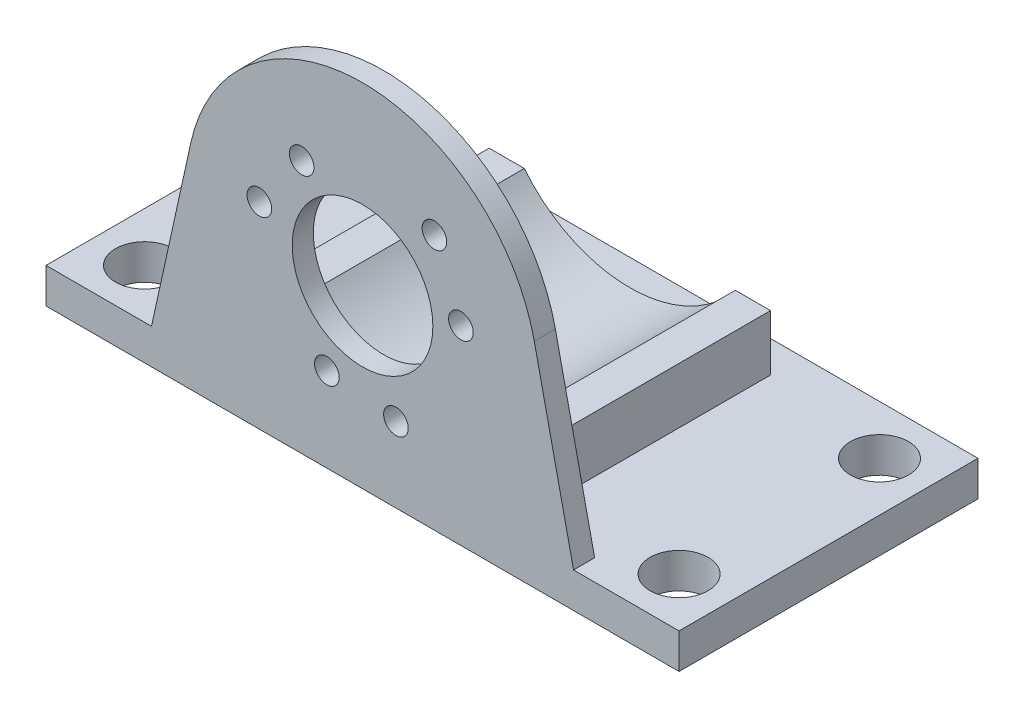
SolidWorks part; units mm, degrees
material "Plain Carbon Steel"
ref_plane "Front Plane" through (0, 0, 0) normal (0, 0, 1) x (1, 0, 0)
ref_plane "Top Plane" through (0, 0, 0) normal (0, 1, 0) x (1, 0, 0)
ref_plane "Right Plane" through (0, 0, 0) normal (1, 0, 0) x (0, 0, -1)
sketch "Sketch3" plane through (0, 0, 0) normal (0, 1, 0) x (1, 0, 0)
  line L0 (-40.6832, 0) -> (52.6999, 0) construction
  line L1 (-45, 21.25) -> (45, 21.25)
  line L2 (-45, 21.25) -> (-45, -21.25)
  line L3 (-45, -21.25) -> (45, -21.25)
  line L4 (45, 21.25) -> (45, -21.25)
  line L5 (0, 26.2262) -> (0, -26.6116) construction
  circle A0 centre (-38, 14.25) radius 4.125
  circle A4 centre (38, 14.25) radius 4.125
  circle A5 centre (38, -14.25) radius 4.125
  circle A6 centre (-38, -14.25) radius 4.125
  point P0 (0, -21.25)
  point P5 (45, 0)
  dimension "D5" = 8.25
  dimension "D1" = 42.5
  dimension "D2" = 90
  dimension "D3" = 7
  dimension "D4" = 7
extrude "Boss-Extrude1" add sketch "Sketch3" along normal blind 5
sketch "Sketch4" plane through (0, 0, 21.25) normal (0, 0, 1) x (1, 0, 0)
  line L2 (30, 5) -> (24.4157, 30.3735)
  line L3 (-30, 5) -> (-24.4157, 30.3735)
  line L4 (-45, 5) -> (45, 5) construction
  line L6 (-30, 5) -> (30, 5)
  circle A1 centre (0, 25) radius 19
  circle A2 centre (0, 25) radius 3
  circle A3 centre (13.9904, 27.0801) radius 1.75
  circle A4 centre (10.2192, 36.3473) radius 1.75
  circle A5 centre (-8.6549, 36.0875) radius 1.75
  circle A6 centre (-14.6673, 27.9923) radius 1.75
  circle A7 centre (-5.0673, 12.0109) radius 1.75
  circle A8 centre (4.7494, 10.6747) radius 1.75
  circle A9 centre (0, 25) radius 10
  arc A10 (24.4157, 30.3735) -> (-24.4157, 30.3735) centre (0, 25) ccw
  point P8 (0, 25)
  line M7 (45, 5) -> (-45, 5)
  dimension "D1" = 38
  dimension "D2" = 6
  dimension "D3" = 3.5
  dimension "D4" = 13.9904
  dimension "D5" = 2.0801
  dimension "D6" = 4.7494
  dimension "D8" = 12.9891
  dimension "D17" = 20
  dimension "D18" = 50
  dimension "D7" = 14.3253
  dimension "D10" = 2.9923
  dimension "D9" = 5.0673
  dimension "D11" = 14.6673
  dimension "D12" = 8.6549
  dimension "D13" = 11.0875
  dimension "D14" = 11.3473
  dimension "D15" = 10.2192
  dimension "D16" = 25
  dimension "D19" = 15
  dimension "D20" = 15
extrude "Boss-Extrude2" add sketch "Sketch4" against normal blind 3 contours A1 A8 A7 A6 A5 A4 A3 A2 | A1 L3 L2 M7 region at (0, 5.75, 21.25) region at (-18.4626, 25, 21.25)
sketch "Sketch5" plane through (0, 0, 18.25) normal (0, 0, -1) x (-1, 0, 0)
  line L1 (-15, 12.9351) -> (-15, 0)
  line L5 (-45, 0) -> (45, 0) construction
  line L7 (-15, 0) -> (15, 0)
  line L9 (15, 0) -> (15, 12.9351)
  line L11 (-20, 12.9351) -> (20, 12.9351)
  line L12 (-20, 12.9351) -> (-20, 0)
  line L13 (-20, 0) -> (20, 0)
  line L14 (20, 12.9351) -> (20, 0)
  circle A3 centre (0, 25) radius 10 construction
  circle A4 centre (0, 25) radius 10
  circle A5 centre (0, 25) radius 19.25
  line M36 (-30, 5) -> (30, 5)
  dimension "D2" = 30
  dimension "D1" = 38.5
  dimension "D3" = 5
extrude "Boss-Extrude3" add sketch "Sketch5" along normal blind 35 contours A5 L1 L9 M36 | L11 L12 L1 M36 | L14 L11 L9 M36 region at (0, 5.4397, 18.25) region at (17.5, 8.9675, 18.25) region at (-17.5, 8.9675, 18.25)
